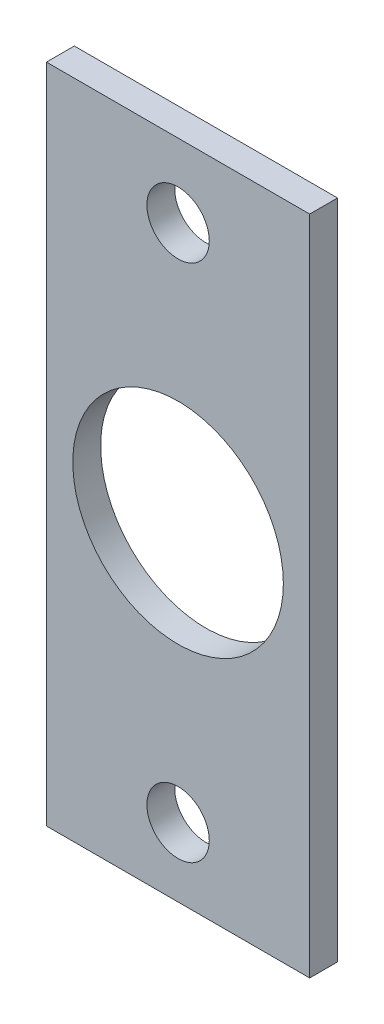
SolidWorks part; units mm, degrees
ref_plane "Front" through (0, 0, 0) normal (0, 0, 1) x (1, 0, 0)
ref_plane "Top" through (0, 0, 0) normal (0, 1, 0) x (1, 0, 0)
ref_plane "Right" through (0, 0, 0) normal (1, 0, 0) x (0, 0, -1)
sketch "Sketch1" plane through (0, 0, 0) normal (0, 0, 1) x (1, 0, 0)
  line L1 (-158.8932, 102.3639) -> (-57.2932, 102.3639)
  line L2 (-158.8932, 102.3639) -> (-158.8932, 0.7639)
  line L3 (-158.8932, 0.7639) -> (-57.2932, 0.7639)
  line L4 (-57.2932, 102.3639) -> (-57.2932, 0.7639)
  point P4 (0, 0)
  dimension "D1" = 101.6
  dimension "D2" = 101.6
extrude "Boss-Extrude1" add sketch "Sketch1" along normal blind 1.5875
sketch "Sketch2" plane through (0, 0, 1.5875) normal (0, 0, 1) x (1, 0, 0)
  circle A0 centre (-108.0932, 51.5639) radius 6
  circle A1 centre (-108.0932, 51.5639) radius 14.7963
  circle A2 centre (-119.1588, 61.3866) radius 2.9721
  point P2 (0, 0)
  dimension "D1" = 12
  dimension "D2" = 29.5927
extrude "Cut-Extrude1" cut sketch "Sketch2" against normal through all contours A0
sketch "Sketch4" plane through (0, 0, 1.5875) normal (0, 0, 1) x (1, 0, 0)
  circle A0 centre (-108.0932, 51.5639) radius 14.7963 construction
  circle A1 centre (-108.0932, 66.3602) radius 1.778
  circle A3 centre (-108.0932, 36.7676) radius 1.778
  dimension "D1" = 29.5927
  dimension "D2" = 3.556
  dimension "D3" = 3.556
extrude "Cut-Extrude2" cut sketch "Sketch4" against normal through all
sketch "Sketch5" plane through (0, 0, 1.5875) normal (0, 0, 1) x (1, 0, 0)
  line L4 (-158.8932, 0.7639) -> (-57.2932, 0.7639) construction
  line L6 (-57.2932, 102.3639) -> (-158.8932, 102.3639) construction
  line L8 (-158.8932, 102.3639) -> (-115.5932, 102.3639)
  line L9 (-158.8932, 102.3639) -> (-158.8932, 0.7639)
  line L10 (-158.8932, 0.7639) -> (-115.5932, 0.7639)
  line L11 (-115.5932, 102.3639) -> (-115.5932, 0.7639)
  line L13 (-57.2932, 102.3639) -> (-100.5932, 102.3639)
  line L14 (-57.2932, 102.3639) -> (-57.2932, 0.7639)
  line L15 (-57.2932, 0.7639) -> (-100.5932, 0.7639)
  line L16 (-100.5932, 102.3639) -> (-100.5932, 0.7639)
extrude "Cut-Extrude4" cut sketch "Sketch5" against normal through all
sketch "Sketch10" plane through (0, 0, 1.5875) normal (0, 0, 1) x (1, 0, 0)
  line L0 (-100.5932, 102.3639) -> (-100.5932, 0.7639) construction
  line L1 (-115.5932, 102.3639) -> (-100.5932, 102.3639)
  line L2 (-115.5932, 102.3639) -> (-115.5932, 70.5472)
  line L3 (-115.5932, 70.5472) -> (-100.5932, 70.5472)
  line L4 (-100.5932, 102.3639) -> (-100.5932, 70.5472)
  line L5 (-115.5932, 0.7639) -> (-115.5932, 102.3639) construction
  line L6 (-100.5932, 0.7639) -> (-115.5932, 0.7639)
  line L7 (-100.5932, 0.7639) -> (-100.5932, 32.8454)
  line L8 (-100.5932, 32.8454) -> (-115.5932, 32.8454)
  line L9 (-115.5932, 0.7639) -> (-115.5932, 32.8454)
extrude "Cut-Extrude5" cut sketch "Sketch10" against normal through all
